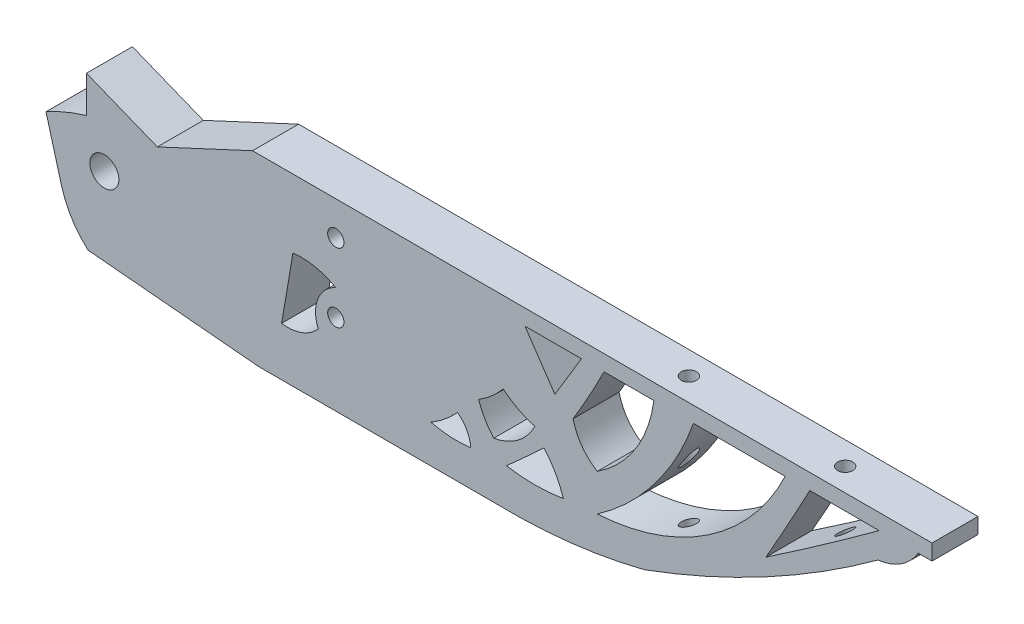
SolidWorks part; units mm, degrees
ref_plane "Front Plane" through (0, 0, 0) normal (0, 0, 1) x (1, 0, 0)
ref_plane "Top Plane" through (0, 0, 0) normal (0, 1, 0) x (1, 0, 0)
ref_plane "Right Plane" through (0, 0, 0) normal (1, 0, 0) x (0, 0, -1)
sketch "Sketch1" plane through (0, 0, 0) normal (0, 0, 1) x (1, 0, 0)
  line L1 (120.65, 25.4) -> (-120.65, 25.4)
  line L2 (120.65, 25.4) -> (120.65, -25.4)
  line L3 (120.65, -25.4) -> (-120.65, -25.4)
  line L4 (-120.65, 25.4) -> (-120.65, -25.4)
  line L5 (120.65, 25.4) -> (-120.65, -25.4) construction
  line L6 (120.65, -25.4) -> (-120.65, 25.4) construction
  point P0 (0, 0)
  dimension "D1" = 241.3
  dimension "D2" = 50.8
extrude "Boss-Extrude1" add sketch "Sketch1" along normal blind 12.7
sketch "Sketch3" plane through (0, 0, 12.7) normal (0, 0, 1) x (1, 0, 0)
  line L0 (0, 0) -> (-120.65, 0) construction
  line L1 (-120.65, 25.4) -> (-120.65, -25.4) construction
  circle A0 centre (-107.95, 0) radius 4
  dimension "D2" = 8
  dimension "D1" = 12.7
extrude "Cut-Extrude1" cut sketch "Sketch3" against normal through all
sketch "Sketch5" plane through (0, 0, 12.7) normal (0, 0, 1) x (1, 0, 0)
  line L0 (-120.65, -25.4) -> (120.65, -25.4) construction
  line L1 (-111.232, -5.4361) -> (-109.6883, -6.1074)
  line L2 (-107.95, 6.35) -> (-67.0151, 25.4)
  line L3 (120.65, 25.4) -> (-120.65, 25.4) construction
  line L4 (-67.0151, 25.4) -> (-120.65, 25.4)
  line L5 (-120.65, 25.4) -> (-120.65, -25.4)
  line L6 (-120.65, -25.4) -> (-65.3282, -25.4)
  line L7 (120.65, 13.8537) -> (120.65, -25.4)
  line L8 (120.65, -25.4) -> (0, -25.4)
  line L9 (120.65, 13.8537) -> (105.7036, 13.8537)
  line L13 (-112.4482, 4.482) -> (-117.3177, 9.3339)
  line L14 (-112.4482, -21.1143) -> (-65.3282, -25.4)
  arc A0 (0, -25.4) -> (105.7036, 13.8537) centre (3.5611, 126.9584) ccw
  arc A1 (-109.9582, -6.0241) -> (-114.0227, -1.8561) centre (-107.95, 0) ccw construction
  arc A2 (-107.95, 6.35) -> (-112.4482, 4.482) centre (-107.95, 0) ccw
  arc A5 (-117.3177, 9.3339) -> (-112.4482, -21.1143) centre (-96.4004, -2.9344) ccw
  point P15 (-116.1445, -2.9908)
  line M3 (-120.65, 25.4) -> (-120.65, -25.4)
  line M4 (-120.65, -25.4) -> (120.65, -25.4)
  line M5 (120.65, -25.4) -> (120.65, 25.4)
  line M6 (120.65, 25.4) -> (-120.65, 25.4)
  dimension "D1" = 152.4
  dimension "D2" = 12.7
  dimension "D3" = 45.1505
  dimension "D4" = 45.9039
extrude "Cut-Extrude2" cut sketch "Sketch5" against normal through all contours A2 L2 L1 M6 M3 M4 | A0 L8 M5 | A5 L5 L14 M4 region at (-102.0317, 17.7416, 12.7) region at (-105.9894, -22.0132, 12.7) region at (91.2141, -11.3337, 12.7)
sketch "Sketch6" plane through (0, 0, 12.7) normal (0, 0, 1) x (1, 0, 0)
  line L0 (-107.95, 0) -> (87.8661, 0) construction
  arc A0 (7.1222, -25.4) -> (105.7036, 13.8537) centre (3.5611, 126.9584) ccw construction
  circle A1 centre (19.05, 0) radius 3.1347
  dimension "D1" = 127
sketch "Sketch7" plane through (0, 0, 0) normal (0, 0, -1) x (-1, 0, 0)
  line L0 (44.0204, -2.9977) -> (44.0204, 16.0523) construction
  point P3 (44.0204, -2.9977)
  point P4 (44.0204, 16.0523)
  dimension "D1" = 19.05
sketch "Sketch8" plane through (0, 0, 0) normal (0, 0, -1) x (-1, 0, 0)
  point P0 (44.0204, 16.0523)
  point P3 (44.0204, -2.9977)
hole_wizard "#8 Clearance Hole1" positions "Sketch8" profile "Sketch9" hole size "#8" standard "ANSI Inch" end condition through all
sketch "Sketch9" plane through (-44.0204, 16.0523, 0) normal (1, 0, 0) x (0, 1, 0)
  line L0 (0, 0) -> (0, 12.7)
  line L1 (0, 12.7) -> (2.2479, 12.7)
  line L2 (2.2479, 12.7) -> (2.2479, 0)
  line L5 (2.2479, 0) -> (0, 0)
  line L11 (0, -6.35) -> (0, 107.95) construction
  dimension "Thru Hole Dia." = 4.4958
  dimension "Thru Hole Depth" = 12.7
ref_plane "Plane1" through (-114.3, 0, 0) normal (-1, 0, 0) x (0, 0, 1)
sketch "Sketch10" plane through (-114.3, 0, 0) normal (-1, 0, 0) x (0, 0, 1)
  line L0 (0, 0) -> (12.7, 0) construction
  line L1 (12.7, -3.1347) -> (12.7, 3.1347) construction
  circle A0 centre (6.0894, 0) radius 1.905
  dimension "D1" = 3.81
sketch "Sketch11" plane through (0, 0, 12.7) normal (0, 0, 1) x (1, 0, 0)
  line L0 (-93.8249, 12.9234) -> (-109.4459, 12.9234) construction
  line L1 (-107.95, 6.35) -> (-67.0151, 25.4) construction
  line L2 (-109.4459, 12.9234) -> (-109.4459, 11.5568) construction
  line L3 (-93.8249, 12.9234) -> (-109.4459, 5.6538)
  line L10 (-119.777, -9.3826) -> (-115.4906, -1.5141)
  line L11 (-115.4906, -1.5141) -> (-109.4459, 5.6538)
  line L12 (-124.0726, 6.1903) -> (-119.777, -9.3826)
  arc A0 (-117.3177, 9.3339) -> (-112.4482, -21.1143) centre (-96.4004, -2.9344) ccw construction
  circle A1 centre (-107.95, 0) radius 4 construction
  arc A4 (-124.0726, 6.1903) -> (-93.8249, 12.9234) centre (-97.649, -41.2057) cw
  dimension "D2" = 5.6538
extrude "Boss-Extrude2" add sketch "Sketch11" against normal up to surface (12.7 mm away) up to face at (-46.2683, 16.0523, 0)
sketch "Sketch18" plane through (0, 25.4, 0) normal (0, 1, 0) x (1, 0, 0)
  circle A0 centre (90.3152, -6.35) radius 2.0828
extrude "Cut-Extrude9" cut sketch "Sketch18" against normal through all contours A0
sketch "Sketch19" plane through (0, 0, 12.7) normal (0, 0, 1) x (1, 0, 0)
  line L3 (86.8867, 21.0579) -> (106.0483, 21.0579)
  line L4 (54.7502, 21.0579) -> (80.0838, 21.0579)
  line L5 (43.8283, 21.0579) -> (30.0654, 21.0579)
  line L6 (21.5195, 21.0579) -> (8.2267, 21.0579)
  line L7 (8.2267, 21.0579) -> (16.4852, 8.8568)
  line L8 (16.4852, 8.8568) -> (23.8201, 21.0579)
  line L9 (23.8201, 21.0579) -> (21.5195, 21.0579)
  arc A0 (106.0483, 21.0579) -> (74.7548, -0.9382) centre (-476.4178, 816.4626) cw
  arc A1 (86.8867, 21.0579) -> (74.7548, -0.9382) centre (-617.5859, 395.2635) cw
  arc A2 (80.0838, 21.0579) -> (28.1833, -13.9058) centre (24.5582, 47.4779) cw
  arc A3 (28.1833, -13.9058) -> (54.7502, 21.0579) centre (-12.7332, 44.7595) ccw
  arc A4 (30.0654, 21.0579) -> (21.5195, 5.5624) centre (-173.1779, 123.0437) cw
  arc A5 (43.8283, 21.0579) -> (28.1833, -3.6987) centre (9.3178, 25.5453) cw
  arc A6 (28.1833, -3.6987) -> (21.5195, 5.5624) centre (35.8652, 8.8568) cw
  arc A7 (3.09, -14.9046) -> (13.4624, -5.4583) centre (-508.9074, 557.7064) ccw
  arc A8 (13.4624, -5.4583) -> (18.8338, -14.9046) centre (-5.5007, -22.4915) cw
  arc A9 (18.8338, -14.9046) -> (3.09, -14.9046) centre (10.9619, 32.5583) cw
  arc A10 (2.2235, 3.0165) -> (-4.5776, -2.8864) centre (-19.0872, 20.7005) cw
  arc A11 (2.2235, 3.0165) -> (10.9619, -1.539) centre (16.8059, 20.3296) ccw
  arc A12 (10.9619, -1.539) -> (-0.4071, -10.0726) centre (-3.0644, 5.3078) cw
  arc A13 (-4.5776, -2.8864) -> (-0.4071, -10.0726) centre (15.1613, 3.7659) ccw
  arc A14 (-10.4164, -8.9177) -> (-6.7592, -15.5263) centre (-15.593, -16.0987) cw
  arc A15 (-6.7592, -15.5263) -> (-17.7308, -14.9046) centre (-10.6309, 13.2663) cw
  arc A16 (-17.7308, -14.9046) -> (-10.4164, -8.9177) centre (-33.6495, 12.0056) ccw
extrude "Cut-Extrude10" cut sketch "Sketch19" against normal through all
pattern_linear "LPattern1" [suppressed] count 5 spacing 6.35 of bodies 117
sketch "Sketch20" plane through (0, 0, 12.7) normal (0, 0, 1) x (1, 0, 0)
  line L0 (-112.9039, 9.7778) -> (-112.9039, 20.995)
  line L2 (-112.9039, 20.995) -> (-92.9368, 13.0011)
  line L3 (-92.9368, 13.0011) -> (-112.9039, 9.7778)
extrude "Boss-Extrude3" add sketch "Sketch20" against normal up to vertex (12.7 mm away) up to point (-124.0726, 6.1903, 0)
sketch "Sketch22" plane through (0, 0, 0) normal (0, 0, -1) x (-1, 0, 0)
  line L0 (-120.65, 21.0579) -> (-116.84, 21.0579)
  line L1 (-120.65, 13.8537) -> (-120.65, 25.4) construction
  line L10 (-120.65, 21.0579) -> (-120.65, 13.8537)
  line L11 (-120.65, 13.8537) -> (-105.7036, 13.8537)
  arc A0 (-116.84, 21.0579) -> (-105.7036, 13.8537) centre (-104.0685, 28.5907) ccw
  dimension "D18" = 14.8275
  dimension "D1" = 3.81
extrude "Cut-Extrude12" cut sketch "Sketch22" against normal through all
sketch "Sketch23" plane through (0, 0, 0) normal (0, 0, -1) x (-1, 0, 0)
  line L2 (-120.65, 21.0579) -> (-120.65, 25.4) construction
  arc A5 (-105.7036, 13.8537) -> (-7.1222, -25.4) centre (-3.5611, 126.9584) ccw
  arc A6 (-105.7036, 13.8537) -> (-41.2201, -20.7154) centre (49.027, 225.0536) ccw
  arc M3 (-105.7036, 13.8537) -> (-7.1222, -25.4) centre (-3.5611, 126.9584) ccw
  dimension "D1" = 152.4
  dimension "D2" = 261.8148
  dimension "D3" = 79.4299
extrude "Cut-Extrude13" cut sketch "Sketch23" against normal through all contours A6 M3 region at (74.7893, -5.9071, 0)
sketch "Sketch24" plane through (0, 0, 0) normal (0, 0, -1) x (-1, 0, 0)
  line L0 (44.0204, -2.9977) -> (44.0204, 16.0523) construction
  line L1 (-80.0838, 21.0579) -> (-54.7502, 21.0579) construction
  arc A0 (44.0204, 4.1309) -> (55.876, 6.5273) centre (53.6319, -12.8946) cw
  arc A1 (55.876, 6.5273) -> (59.0043, -11.8919) centre (1722.1416, 280.0452) ccw
  arc A2 (59.0043, -11.8919) -> (48.8565, -8.1533) centre (57.3207, -0.8203) cw
  arc A3 (48.8565, -8.1533) -> (44.0204, 4.1309) centre (40.2964, -4.4292) ccw
  dimension "D1" = 19.5512
  dimension "D2" = 1688.5654
  dimension "D3" = 11.1989
  dimension "D4" = 9.3351
  dimension "D5" = 22.5656
  dimension "D6" = 31.1257
  dimension "D7" = 35.901
  dimension "D8" = 38.1452
  dimension "D9" = 39.5899
  dimension "D10" = 41.2735
  dimension "D11" = 258.9872
extrude "Cut-Extrude14" cut sketch "Sketch24" against normal through all
sketch "Sketch29" plane through (0, 25.4, 0) normal (0, 1, 0) x (1, 0, 0)
  line L0 (120.65, -12.7) -> (120.65, 0) construction
  circle A0 centre (47.1354, -6.35) radius 2.0828
  point P0 (120.65, -6.35)
  point P3 (47.1354, -6.35)
  dimension "D2" = 4.1656
  dimension "D1" = 73.5146
extrude "Cut-Extrude19" cut sketch "Sketch29" against normal through all contours A0
